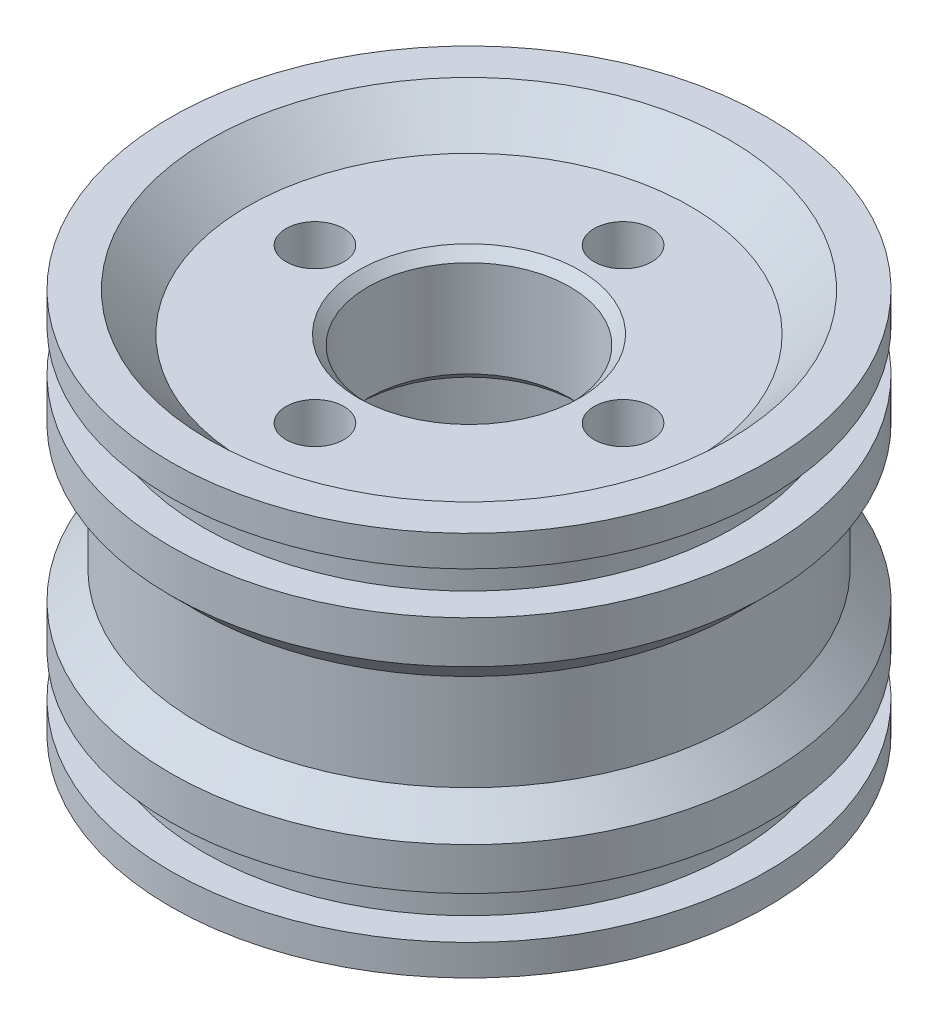
SolidWorks part; units mm, degrees
ref_plane "前视基准面" through (0, 0, 0) normal (0, 0, 1) x (1, 0, 0)
ref_plane "上视基准面" through (0, 0, 0) normal (0, 1, 0) x (1, 0, 0)
ref_plane "右视基准面" through (0, 0, 0) normal (1, 0, 0) x (0, 0, -1)
other "Configuration Table"
sketch "草图1" plane through (0, 0, 0) normal (0, 1, 0) x (1, 0, 0)
  circle A0 centre (0, 0) radius 15.5
  dimension "D1" = 31
extrude "凸台-拉伸1" add sketch "草图1" along normal mid plane 20
sketch "草图2" plane through (0, 0, 0) normal (0, 0, 1) x (1, 0, 0)
  line L0 (15.5, -10) -> (15.5, 10) construction
  line L1 (15.5, 8.4) -> (0, 8.4) construction
  line L2 (15.5, 8.4) -> (15.5, 6.2) construction
  line L3 (15.5, 6.2) -> (0, 6.2) construction
  line L4 (0, 8.4) -> (0, 6.2) construction
  line L5 (15.5, 10) -> (-15.5, 10) construction
  line L7 (15.5, 8.4) -> (13.8, 8.4)
  line L8 (15.5, 8.4) -> (15.5, 6.2)
  line L9 (15.5, 6.2) -> (13.8, 6.2)
  line L10 (13.8, 8.4) -> (13.8, 6.2)
  dimension "D1" = 2.2
  dimension "D2" = 1.6
  dimension "D3" = 1.7
revolve "切除-旋转1" cut sketch "草图2" angle 360 about L4
mirror "镜向1" about plane through (0, 0, 0) normal (0, 1, 0) of "切除-旋转1"
sketch "草图4" plane through (0, -10, 0) normal (0, -1, 0) x (1, 0, 0)
  circle A0 centre (0, 0) radius 11.5
  dimension "D1" = 23
extrude "切除-拉伸1" cut sketch "草图4" against normal blind 12
sketch "草图5" plane through (0, 10, 0) normal (0, 1, 0) x (1, 0, 0)
  circle A0 centre (0, 0) radius 5.25
  dimension "D1" = 10.5
extrude "切除-拉伸2" cut sketch "草图5" against normal blind 15 contours A0 region at (0, 10, 0)
chamfer "倒角1" distance 2 angle 45 1 edges at (0, -10, -11.5)
sketch "草图6" plane through (0, 10, 0) normal (0, 1, 0) x (1, 0, 0)
  circle A0 centre (0, 0) radius 5
  circle A1 centre (0, 0) radius 11.5
  dimension "D1" = 23
  dimension "D2" = 10
extrude "切除-拉伸3" cut sketch "草图6" against normal blind 2
chamfer "倒角2" distance 2 angle 45 1 edges at (0, 10, 11.5)
ref_axis "基准轴1" through (0, 2, 0) along (0, 1, 0)
sketch "草图7" plane through (0, 0, 0) normal (1, 0, 0) x (0, 0, -1)
  line L0 (15.5, -6.2) -> (15.5, 6.2) construction
  line L1 (14, -4) -> (15.5, -4)
  line L2 (14, -4) -> (14, 4)
  line L3 (14, 4) -> (15.5, 4)
  line L4 (15.5, -4) -> (15.5, 4)
  line L5 (14, -4) -> (15.5, 4) construction
  line L6 (14, 4) -> (15.5, -4) construction
  point P0 (14.75, 0)
  dimension "D1" = 1.5
  dimension "D2" = 8
sketch "草图8" plane through (0, 2, 0) normal (0, -1, 0) x (1, 0, 0)
  circle A0 centre (-8, 0) radius 1.5
  point P2 (0, 0)
  dimension "D1" = 3
  dimension "D2" = 8
extrude "切除-拉伸4" cut sketch "草图8" against normal blind 10
pattern_circular "阵列(圆周)1" count 4 over 360 about axis through (0, 2, 0) along (0, 1, 0) of "切除-拉伸4"
revolve "切除-旋转2" cut sketch "草图7" angle 360 about axis through (0, 2, 0) along (0, 1, 0)
chamfer "倒角5" distance 1.5 angle 45 2 edges at (0, 4, -14) (0, -4, -14)
chamfer "倒角4" distance 0.5 angle 45 3 edges at (0, 2, -11.5) (0, 8, 5.25) (0, 2, -5.25)
